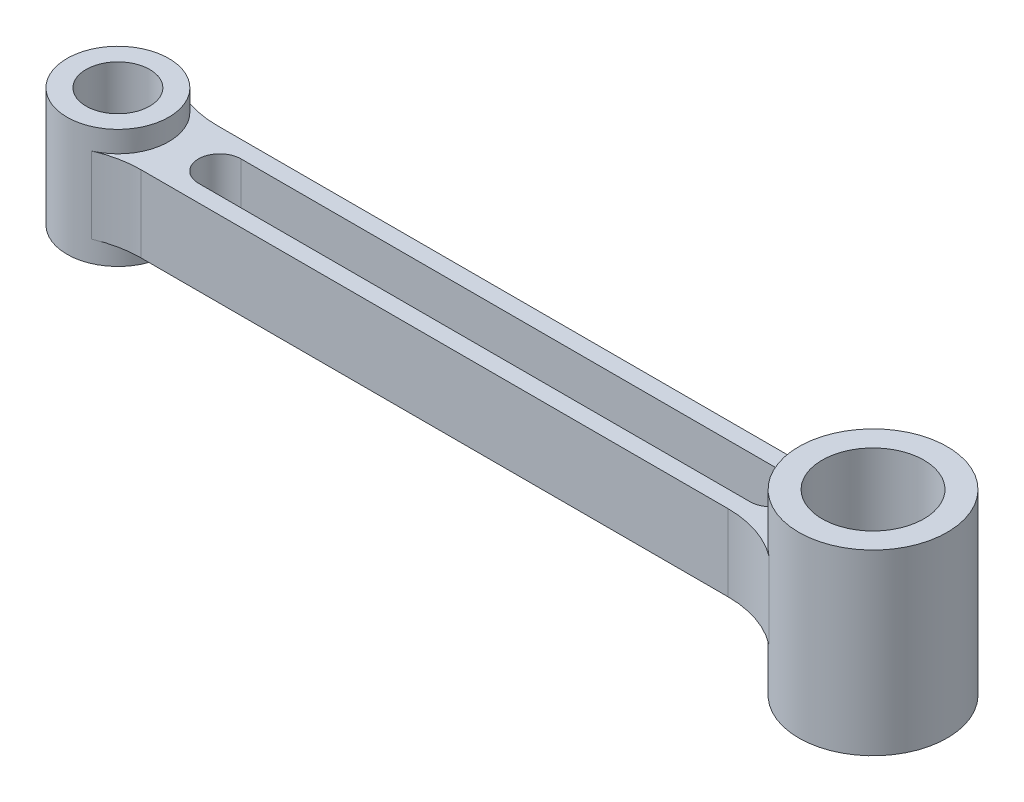
SolidWorks part; units mm, degrees
ref_plane "Front Plane" through (0, 0, 0) normal (0, 0, 1) x (1, 0, 0)
ref_plane "Top Plane" through (0, 0, 0) normal (0, 1, 0) x (1, 0, 0)
ref_plane "Right Plane" through (0, 0, 0) normal (1, 0, 0) x (0, 0, -1)
sketch "Sketch1" plane through (0, 0, 0) normal (0, 1, 0) x (1, 0, 0)
  line L0 (-89, 0) -> (89, 0) construction
  line L1 (-74.6125, 9) -> (63.8355, 9)
  line L2 (-74.6125, -9) -> (63.8355, -9)
  circle A0 centre (-89, 0) radius 12
  circle A1 centre (-89, 0) radius 7.5
  circle A2 centre (89, 0) radius 17.5
  circle A3 centre (89, 0) radius 12
  arc A4 (-84.2042, 11) -> (-74.6125, 9) centre (-74.6125, 33) ccw
  arc A5 (78.3885, 13.9157) -> (63.8355, 9) centre (63.8355, 33) cw
  arc A6 (-84.2042, -11) -> (-74.6125, -9) centre (-74.6125, -33) cw
  arc A7 (78.3885, -13.9157) -> (63.8355, -9) centre (63.8355, -33) ccw
  dimension "D3" = 24
  dimension "D4" = 15
  dimension "D5" = 35
  dimension "D6" = 24
  dimension "D8" = 24
  dimension "D9" = 24
  dimension "D1" = 178
  dimension "D2" = 89
  dimension "D7" = 9
  dimension "D10" = 89
extrude "Boss-Extrude1" add sketch "Sketch1" along normal mid plane 28 contours A1 A0 | A0 | A1 region at (-79.2453, 0, -6.3886)
extrude "Boss-Extrude2" add sketch "Sketch1<6>" along normal mid plane 42 separate body contours A2 A3 region at (96.5441, 0, -15.24)
sketch "Sketch1<6>" plane through (0, 0, 0) normal (0, 1, 0) x (1, 0, 0) same geometry as "Sketch1"
extrude "Boss-Extrude3" add sketch "Sketch1<7>" along normal mid plane 18 contours A0 L0 A2 A5 L1 A4 | L0 A0 A6 L2 A7 A2 region at (-2.5464, 0, -4.5847) region at (-2.5464, 0, 4.5847)
sketch "Sketch1<7>" plane through (0, 0, 0) normal (0, 1, 0) x (1, 0, 0) same geometry as "Sketch1"
sketch "Sketch2" plane through (0, 9, 0) normal (0, 1, 0) x (1, 0, 0)
  line L0 (-65, 0) -> (65, 0) construction
  line L1 (-89, 0) -> (89, 0) construction
  line L2 (-65, 5) -> (65, 5)
  line L3 (-65, -5) -> (65, -5)
  arc A0 (-65, 5) -> (-65, -5) centre (-65, 0) ccw
  arc A1 (65, -5) -> (65, 5) centre (65, 0) ccw
  point P4 (0, 0)
  dimension "D1" = 10
  dimension "D2" = 130
  dimension "D3" = 65
  dimension "D4" = 65
extrude "Cut-Extrude1" cut sketch "Sketch2" against normal up to next
